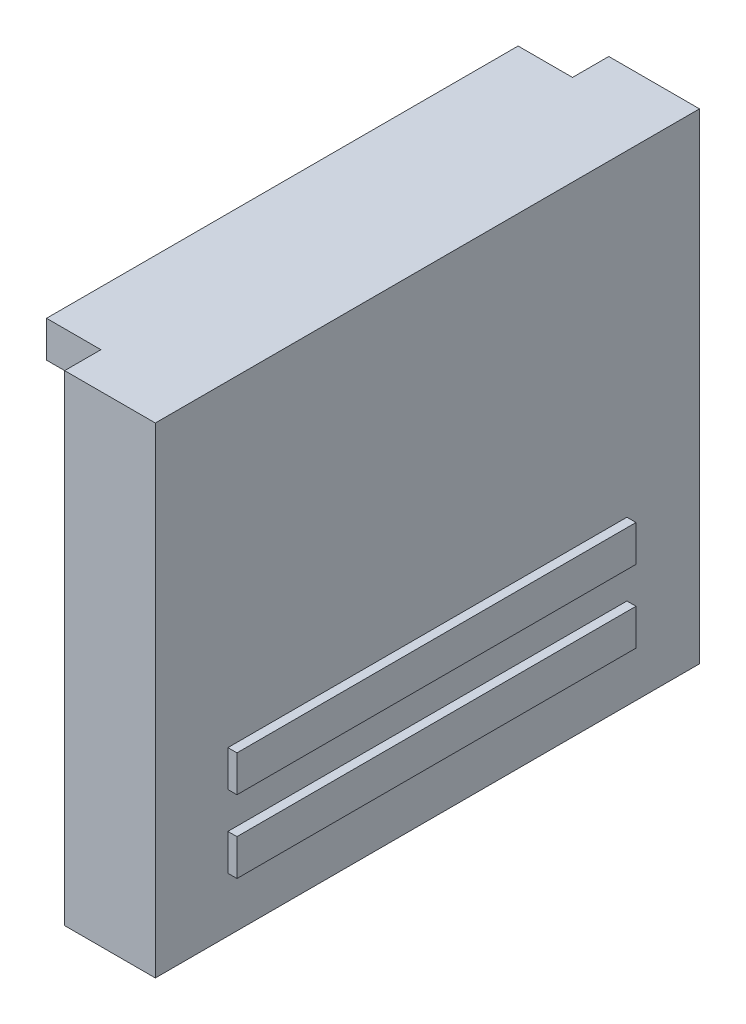
SolidWorks part; units mm, degrees
ref_plane "Front Plane" through (0, 0, 0) normal (0, 0, 1) x (1, 0, 0)
ref_plane "Top Plane" through (0, 0, 0) normal (0, 1, 0) x (1, 0, 0)
ref_plane "Right Plane" through (0, 0, 0) normal (1, 0, 0) x (0, 0, -1)
ref_plane "Plane1" through (181, 0, 0) normal (1, 0, 0) x (0, 0, -1)
sketch "Sketch1" plane through (181, 0, 0) normal (1, 0, 0) x (0, 0, -1)
  line L0 (-134, 37) -> (-134, 63.5)
  line L1 (-134, 63.5) -> (-164, 63.5)
  line L2 (-164, 63.5) -> (-164, 37)
  line L3 (-164, 37) -> (-134, 37)
extrude "Boss-Extrude1" add sketch "Sketch1" along normal mid plane 5
ref_plane "Plane2" through (183.5, 0, 0) normal (1, 0, 0) x (0, 0, -1)
sketch "Sketch2" plane through (183.5, 0, 0) normal (1, 0, 0) x (0, 0, -1)
  line L0 (-138, 40) -> (-138, 42)
  line L1 (-138, 42) -> (-160, 42)
  line L2 (-160, 42) -> (-160, 40)
  line L3 (-160, 40) -> (-138, 40)
  line L4 (-138, 44) -> (-138, 46)
  line L5 (-138, 46) -> (-160, 46)
  line L6 (-160, 46) -> (-160, 44)
  line L7 (-160, 44) -> (-138, 44)
extrude "Boss-Extrude2" add sketch "Sketch2" along normal mid plane 1
ref_plane "Plane3" through (177, 0, 0) normal (1, 0, 0) x (0, 0, -1)
sketch "Sketch3" plane through (177, 0, 0) normal (1, 0, 0) x (0, 0, -1)
  line L0 (-136, 61.5) -> (-136, 63.5)
  line L1 (-136, 63.5) -> (-162, 63.5)
  line L2 (-162, 63.5) -> (-162, 61.5)
  line L3 (-162, 61.5) -> (-136, 61.5)
extrude "Boss-Extrude3" add sketch "Sketch3" along normal mid plane 3
ref_plane "Plane4" through (176, 0, 0) normal (1, 0, 0) x (0, 0, -1)
sketch "Sketch4" plane through (176, 0, 0) normal (1, 0, 0) x (0, 0, -1)
  circle A0 centre (-149, 43) radius 2
extrude "Boss-Extrude4" add sketch "Sketch4" along normal mid plane 5
